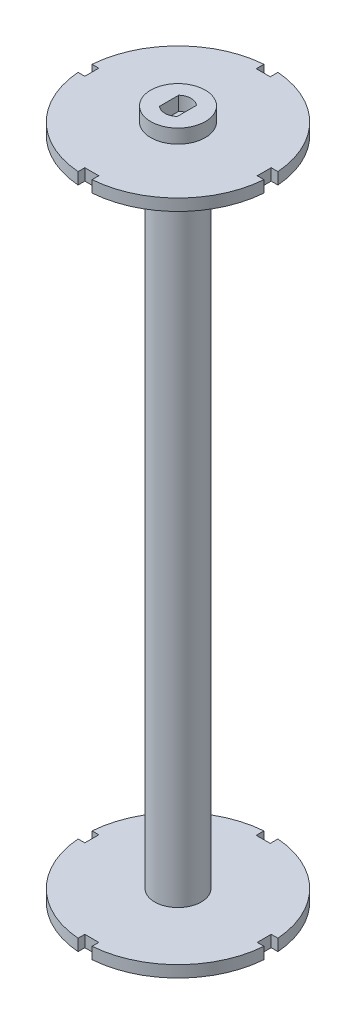
SolidWorks part; units mm, degrees
ref_plane "Front Plane" through (0, 0, 0) normal (0, 0, 1) x (1, 0, 0)
ref_plane "Top Plane" through (0, 0, 0) normal (0, 1, 0) x (1, 0, 0)
ref_plane "Right Plane" through (0, 0, 0) normal (1, 0, 0) x (0, 0, -1)
sketch "Sketch1" plane through (0, 0, 0) normal (0, 1, 0) x (1, 0, 0)
  line L0 (1.9, 2.0567) -> (1.9, -2.0567)
  line L1 (-1.9, -2.0567) -> (-1.9, 2.0567)
  line L2 (-1.9, 2.0567) -> (-1.9, 5.5329)
  line L3 (1.9, 2.0567) -> (1.9, 5.5329)
  line L4 (-1.9, -2.0567) -> (-1.9, -5.5329)
  line L5 (1.9, -2.0567) -> (1.9, -5.5329)
  circle A0 centre (0, 0) radius 2.8
  circle A1 centre (0, 0) radius 5.85
  dimension "D1" = 5.6
  dimension "D4" = 11.7
  dimension "D2" = 1.9
  dimension "D3" = 1.9
extrude "Boss-Extrude1" add sketch "Sketch1" along normal blind 5.5 contours L2 A1 L4 A0 | L3 A1 L2 A0 | L5 A1 L3 A0 | L4 A1 L5 A0 | L1 A0 | L0 A0 region at (2.2655, 0, 0) region at (0, 0, -4.1503) region at (3.6479, 0, 0) region at (0, 0, 4.1503) region at (-3.6479, 0, 0) region at (-2.2655, 0, 0)
sketch "Sketch2" plane through (0, 5.5, 0) normal (0, 1, 0) x (1, 0, 0)
  circle A0 centre (0, 0) radius 20
  dimension "D1" = 40
extrude "Boss-Extrude2" add sketch "Sketch2" against normal blind 2.5
sketch "Sketch3" plane through (0, 3, 0) normal (0, -1, 0) x (1, 0, 0)
  line L2 (-1.9, 2.0567) -> (-1.9, -2.0567)
  line L3 (1.9, -2.0567) -> (1.9, 2.0567)
  line L4 (-1.9, 2.0567) -> (-1.9, -2.0567)
  line L5 (1.9, -2.0567) -> (1.9, 2.0567)
  arc A2 (1.9, 2.0567) -> (-1.9, 2.0567) centre (0, 0) ccw
  arc A3 (-1.9, -2.0567) -> (1.9, -2.0567) centre (0, 0) ccw
  arc A4 (1.9, 2.0567) -> (-1.9, 2.0567) centre (0, 0) ccw
  arc A5 (-1.9, -2.0567) -> (1.9, -2.0567) centre (0, 0) ccw
  dimension "D1" = 0
extrude "Cut-Extrude1" cut sketch "Sketch3" against normal blind 8
sketch "Sketch4" plane through (0, 5.5, 0) normal (0, 1, 0) x (1, 0, 0)
  line L0 (0, 21.3) -> (0, 0) construction
  line L1 (-1.5, 21.3) -> (1.5, 21.3)
  line L2 (-1.5, 21.3) -> (-1.5, 18.3)
  line L3 (-1.5, 18.3) -> (1.5, 18.3)
  line L4 (1.5, 21.3) -> (1.5, 18.3)
  line L5 (0, 0) -> (32.685, 0) construction
  line L6 (0, 0) -> (0, -28.3806) construction
  line L7 (0, 0) -> (-25.3685, 0) construction
  line L9 (18.5, 1.5) -> (21.5, 1.5)
  line L10 (18.5, 1.5) -> (18.5, -1.5)
  line L11 (18.5, -1.5) -> (21.5, -1.5)
  line L12 (21.5, 1.5) -> (21.5, -1.5)
  line L13 (18.5, 1.5) -> (21.5, -1.5) construction
  line L14 (18.5, -1.5) -> (21.5, 1.5) construction
  line L15 (-1.5, -18.5) -> (1.5, -18.5)
  line L16 (-1.5, -18.5) -> (-1.5, -21.5)
  line L17 (-1.5, -21.5) -> (1.5, -21.5)
  line L18 (1.5, -18.5) -> (1.5, -21.5)
  line L19 (-1.5, -18.5) -> (1.5, -21.5) construction
  line L20 (-1.5, -21.5) -> (1.5, -18.5) construction
  line L21 (-21.5, 1.5) -> (-18.5, 1.5)
  line L22 (-21.5, 1.5) -> (-21.5, -1.5)
  line L23 (-21.5, -1.5) -> (-18.5, -1.5)
  line L24 (-18.5, 1.5) -> (-18.5, -1.5)
  line L25 (-21.5, 1.5) -> (-18.5, -1.5) construction
  line L26 (-21.5, -1.5) -> (-18.5, 1.5) construction
  circle A0 centre (0, 0) radius 20 construction
  point P12 (20, 0)
  point P17 (0, -20)
  point P22 (-20, 0)
  dimension "D1" = 3
  dimension "D2" = 3
  dimension "D3" = 18.3
  dimension "D4" = 3
  dimension "D5" = 3
  dimension "D6" = 3
  dimension "D7" = 3
  dimension "D8" = 3
  dimension "D9" = 3
ref_axis "Axis1" through (0, 5.5, 0) along (0, -1, 0)
extrude "Cut-Extrude2" cut sketch "Sketch4" against normal blind 10
sketch "Sketch5" plane through (0, 5.5, 0) normal (0, 1, 0) x (1, 0, 0)
  circle A0 centre (0, 0) radius 5
  dimension "D1" = 10
extrude "Boss-Extrude3" add sketch "Sketch5" along normal blind 140
ref_plane "Plane1" through (0, 75.5, 0) normal (0, 1, 0) x (1, 0, 0)
mirror "Mirror1" about plane through (0, 75.5, 0) normal (0, 1, 0) of "Boss-Extrude2"
mirror "Mirror2" about plane through (0, 75.5, 0) normal (0, 1, 0) of "Cut-Extrude2", "Boss-Extrude1"
